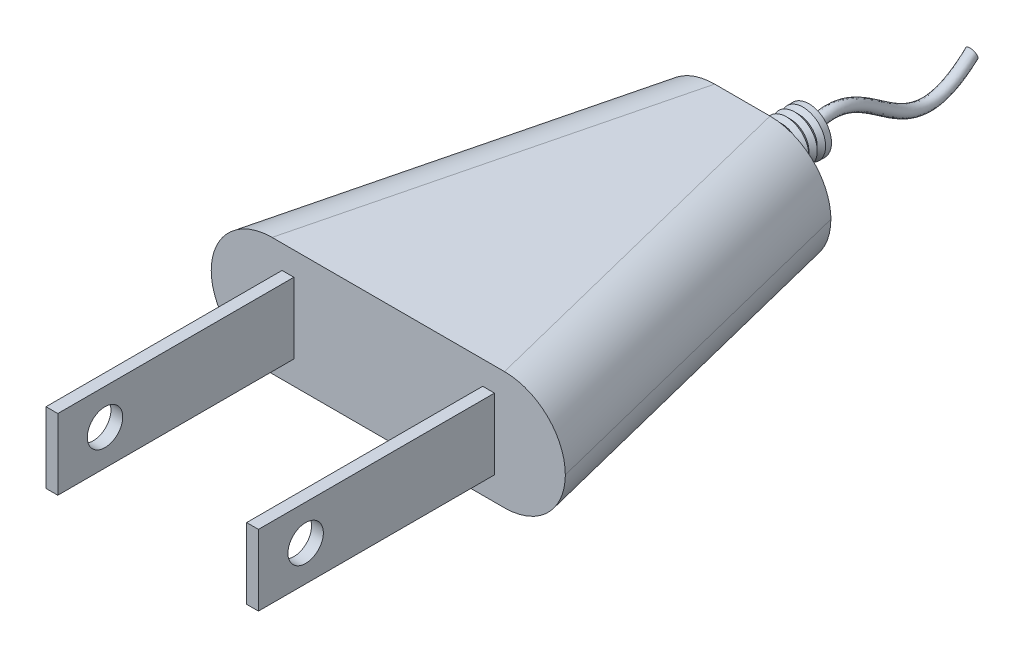
SolidWorks part; units mm, degrees
ref_plane "前视基准面" through (0, 0, 0) normal (0, 0, 1) x (1, 0, 0)
ref_plane "上视基准面" through (0, 0, 0) normal (0, 1, 0) x (1, 0, 0)
ref_plane "右视基准面" through (0, 0, 0) normal (1, 0, 0) x (0, 0, -1)
sketch3d "3D草图9" plane through (0, 0, 0) normal (0, 0, 1) x (1, 0, 0)
  dimension "D1" = 30
sketch "草图1" plane through (0, 0, 0) normal (0, 0, 1) x (1, 0, 0)
  line L0 (0, 79.5033) -> (0, -101.9274) construction
  line L1 (-7.5, -5) -> (7.5, -5)
  line L2 (-7.5, -5) -> (-7.5, 5)
  line L3 (-7.5, 5) -> (7.5, 5)
  line L4 (7.5, -5) -> (7.5, 5)
  line L5 (-111.2464, 0) -> (161.0452, 0) construction
  point P9 (0, 5)
  point P11 (-7.5, 0)
  dimension "D1" = 15
  dimension "D2" = 10
sketch "草图2" plane through (0, 0, 30) normal (0, 0, 1) x (1, 0, 0)
  line L1 (-15, 5) -> (15, 5)
  line L2 (-15, 5) -> (-15, -5)
  line L3 (-15, -5) -> (15, -5)
  line L4 (15, 5) -> (15, -5)
  line L7 (-22.3601, 0) -> (26.439, 0) construction
  line L10 (0, 11.2223) -> (0, -11.7087) construction
  line L11 (0, 200079.5033) -> (0, -200101.9274) construction
  dimension "D1" = 30
  dimension "D2" = 15
  dimension "D3" = 10
  dimension "D4" = 5
loft "放样1" add profiles "草图2", "草图1" connector at (15, 5, 30) connector at (7.5, 5, 0)
fillet "圆角1" radius 5 4 edges
sketch "草图3" plane through (0, 0, 0) normal (1, 0, 0) x (0, 0, -1)
  line L0 (0, 1.9109) -> (1.6076, 1.9109)
  line L1 (0, 0) -> (0, 5) construction
  line L2 (1.6076, 1.9109) -> (1.9611, 1.5574)
  line L3 (1.9611, 1.5574) -> (2.3147, 1.9109)
  line L4 (2.3147, 1.9109) -> (2.6682, 1.5574)
  line L5 (2.6682, 1.5574) -> (3.0218, 1.9109)
  line L6 (3.0218, 1.9109) -> (3.3753, 1.5574)
  line L7 (3.3753, 1.5574) -> (3.7289, 1.9109)
  line L8 (3.7289, 1.9109) -> (4.0824, 1.5574)
  line L9 (4.0824, 1.5574) -> (4.436, 1.9109)
  line L10 (4.436, 1.9109) -> (4.7895, 1.5574)
  line L11 (4.7895, 1.5574) -> (5.1431, 1.9109)
  line L12 (5.1431, 1.9109) -> (5.6431, 1.9109)
  line L13 (5.6431, 1.9109) -> (5.6431, 0)
  line L14 (5.6431, 0) -> (0, 0)
  line L15 (0, 0) -> (0, 1.9109)
  dimension "D1" = 0.5
  dimension "D2" = 0.5
  dimension "D3" = 0.5
  dimension "D4" = 0.5
  dimension "D5" = 0.5
  dimension "D6" = 0.5
  dimension "D7" = 0.5
  dimension "D8" = 0.5
  dimension "D9" = 0.5
  dimension "D10" = 0.5
  dimension "D11" = 0.5
revolve "旋转1" add sketch "草图3" angle 360 about L14
sketch "草图4" plane through (0, 0, 0) normal (1, 0, 0) x (0, 0, -1)
  line L0 (5.6431, -1.9109) -> (5.6431, 1.9109) construction
  spline S0 degree 3 poles (5.6431, 0) (11.0905, 2.4032) (13.3504, -6.9292) (19.4413, -1.2797) knots 0 0 0 0 1 1 1 1
sketch "草图5" plane through (0, 0, -5.6431) normal (0, 0, -1) x (-1, 0, 0)
  circle A0 centre (0, 0) radius 0.5
  dimension "D1" = 1
sweep "扫描1" add profiles "草图5" path "草图4"
sketch "草图6" plane through (0, 0, 30) normal (0, 0, 1) x (1, 0, 0)
  line L0 (-15, 5) -> (-15, -5) construction
  line L1 (-9, 3) -> (-8, 3)
  line L2 (-9, 3) -> (-9, -3)
  line L3 (-9, -3) -> (-8, -3)
  line L4 (-8, 3) -> (-8, -3)
  line L5 (-15, 5) -> (15, 5) construction
  dimension "D1" = 6
  dimension "D2" = 1
  dimension "D3" = 6
  dimension "D4" = 2
extrude "凸台-拉伸1" add sketch "草图6" along normal blind 20 separate body
sketch "草图7" plane through (-8, 0, 0) normal (1, 0, 0) x (0, 0, -1)
  line L0 (-50, -3) -> (-30, -3) construction
  line L1 (-50, -3) -> (-50, 3) construction
  circle A0 centre (-46, 0) radius 1.5
  dimension "D1" = 3
  dimension "D2" = 3
  dimension "D3" = 4
extrude "切除-拉伸1" cut sketch "草图7" against normal blind 1
mirror "镜向5" about plane through (0, 0, 0) normal (1, 0, 0) of bodies 111
